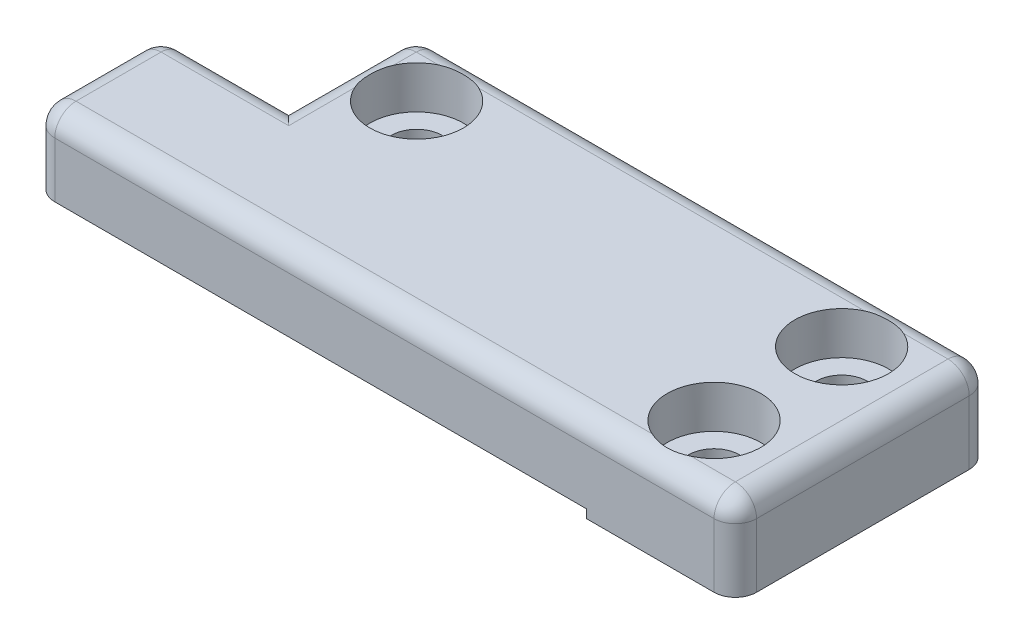
SolidWorks part; units mm, degrees
ref_plane "前基準面" through (0, 0, 0) normal (0, 0, 1) x (1, 0, 0)
ref_plane "上基準面" through (0, 0, 0) normal (0, 1, 0) x (1, 0, 0)
ref_plane "右基準面" through (0, 0, 0) normal (1, 0, 0) x (0, 0, -1)
sketch "草圖1" plane through (0, 0, 0) normal (0, 1, 0) x (1, 0, 0)
  line L1 (-13, -6) -> (20, -6)
  line L2 (-13, -6) -> (-13, 0)
  line L3 (-7, 6) -> (20, 6)
  line L4 (20, -6) -> (20, 6)
  line L5 (-7, 6) -> (-7, 0)
  line L6 (-7, 0) -> (-13, 0)
  line L7 (20, -6) -> (-13, -6) construction
  line L8 (20, -6) -> (20, 6) construction
  line L9 (20, 6) -> (-7, 6) construction
  line L10 (-13, -6) -> (-13, 0) construction
  dimension "D1" = 12
  dimension "D2" = 6
  dimension "D3" = 20
  dimension "D4" = 33
  dimension "D5" = 6
  dimension "D6" = 6
extrude "填料-伸長1" add sketch "草圖1" along normal blind 4
sketch "草圖2" plane through (0, 0, 0) normal (0, 1, 0) x (1, 0, 0)
  line L0 (0, 0) -> (0, 3.015) construction
  line L1 (20, -6) -> (-12, -6) construction
  line L2 (20, -6) -> (20, 6) construction
  line L3 (20, 6) -> (-12, 6) construction
  line L4 (-12, -6) -> (-12, 6) construction
  line L6 (0, 3.015) -> (-4, 3.015) construction
  line L7 (0, 3.015) -> (10, 3.015) construction
  circle A0 centre (-4, 3.015) radius 2.2
  dimension "D1" = 12
  dimension "D2" = 32
extrude "除料-伸長2" cut sketch "草圖2" against normal blind 2 from offset 4
sketch "草圖3" plane through (0, 0, 0) normal (0, 1, 0) x (1, 0, 0)
  line L0 (-7, 0) -> (-13, 0) construction
  line L1 (20, -6) -> (-12, -6) construction
  line L2 (20, -6) -> (20, 6) construction
  line L3 (20, 6) -> (-12, 6) construction
  line L4 (-12, -6) -> (-12, 6) construction
  circle A0 centre (16, -3) radius 2.2
  circle A1 centre (16, 3) radius 2.2
  dimension "D3" = 3
  dimension "D1" = 32
  dimension "D2" = 12
  dimension "D4" = 4
extrude "除料-伸長3" cut sketch "草圖3" against normal blind 2 from offset 4
sketch "草圖4" plane through (0, 0, 0) normal (0, 1, 0) x (1, 0, 0)
  circle A0 centre (-4, 3.015) radius 1.2
  circle A2 centre (16, -3) radius 1.2
extrude "除料-伸長4" cut sketch "草圖4" along normal through all
sketch "草圖5" plane through (0, 0, 0) normal (0, 1, 0) x (1, 0, 0)
  line L0 (20, 6) -> (-7, 6) construction
  line L1 (20, -6) -> (20, 6) construction
  circle A0 centre (16, 3) radius 1.2
  dimension "D1" = 3
  dimension "D2" = 4
extrude "除料-伸長5" cut sketch "草圖5" along normal through all
fillet "圓角1" radius 1 11 edges at (-7, 4, -3) (-10, 4, 0) (-13, 4, 3) (3.5, 4, 6) (20, 4, 0) (6.5, 4, -6) (-13, 2, 0) (-13, 2, 6) (20, 2, 6) (20, 2, -6) (-7, 2, -6)
sketch "草圖6" plane through (0, 0, 0) normal (0, 1, 0) x (1, 0, 0)
  line L0 (19, -6) -> (-12, -6) construction
  line L1 (-13, -6) -> (13, -6)
  line L2 (-13, -6) -> (-13, 0)
  line L3 (-13, 0) -> (13, 0)
  line L4 (13, -6) -> (13, 0)
  line L5 (-7, 0) -> (-7, 5) construction
  dimension "D1" = 26
  dimension "D2" = 6
  dimension "D3" = 0
  dimension "D4" = 6
extrude "除料-伸長8" cut sketch "草圖6" along normal blind 0.4
